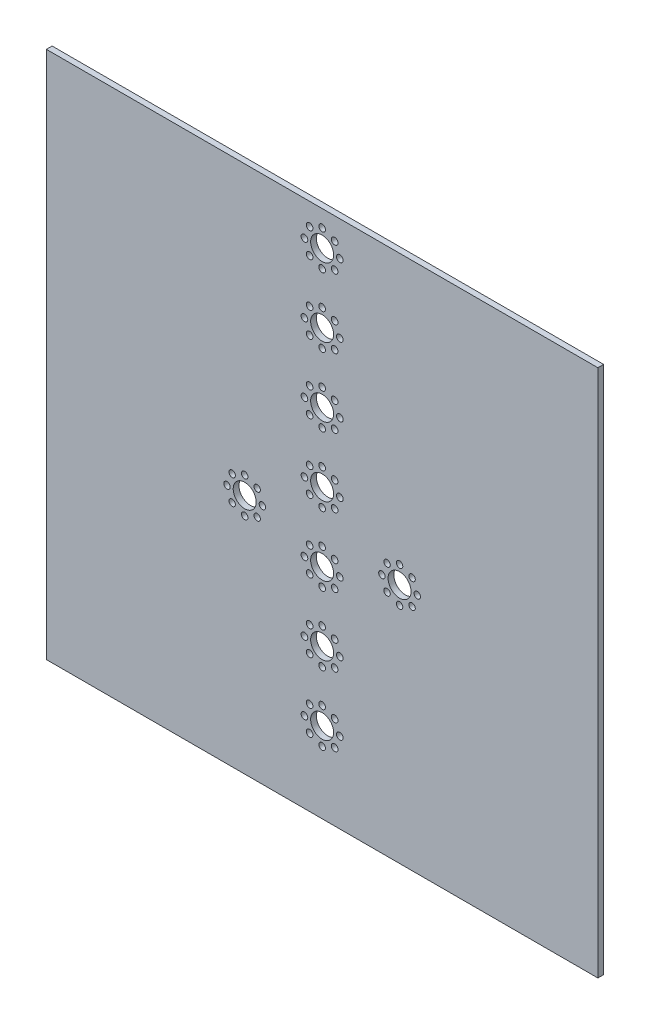
SolidWorks part; units mm, degrees
material "6061-T6 (SS)"
ref_plane "Front Plane" through (0, 0, 0) normal (0, 0, 1) x (1, 0, 0)
ref_plane "Top Plane" through (0, 0, 0) normal (0, 1, 0) x (1, 0, 0)
ref_plane "Right Plane" through (0, 0, 0) normal (1, 0, 0) x (0, 0, -1)
sketch "Sketch1" plane through (0, 0, 0) normal (0, 0, 1) x (1, 0, 0)
  line L1 (0, 0) -> (-304.8, 0)
  line L2 (0, 0) -> (0, -292.1)
  line L3 (0, -292.1) -> (-304.8, -292.1)
  line L4 (-304.8, 0) -> (-304.8, -292.1)
  dimension "D1" = 292.1
  dimension "D2" = 304.8
extrude "Boss-Extrude1" add sketch "Sketch1" along normal blind 3.175
sketch "Sketch2" plane through (0, 0, 0) normal (0, 0, -1) x (-1, 0, 0)
  line L0 (0, -158.75) -> (304.8, -158.75) construction
  line L1 (0, -292.1) -> (0, 0) construction
  line L2 (304.8, 0) -> (304.8, -292.1) construction
  line L3 (304.8, -292.1) -> (0, -292.1) construction
  circle A0 centre (99.822, -158.75) radius 1.778
  point P12 (109.601, -158.75)
  dimension "D2" = 109.601
  dimension "D3" = 3.556
  dimension "D1" = 133.35
  dimension "D5" = 9.779
extrude "Cut-Extrude1" cut sketch "Sketch2" against normal blind 3.175
ref_plane "Plane1" through (-152.4, 0, 0) normal (1, 0, 0) x (0, 0, -1)
mirror "Mirror1" about plane through (-152.4, 0, 0) normal (1, 0, 0) of "Cut-Extrude1"
sketch "Sketch3" plane through (0, 0, 0) normal (0, 0, -1) x (-1, 0, 0)
  line L2 (304.8, -292.1) -> (0, -292.1) construction
  line L3 (0, -292.1) -> (0, 0) construction
  circle A0 centre (109.601, -158.75) radius 6.35
  dimension "D3" = 12.7
  dimension "D1" = 133.35
  dimension "D2" = 109.601
extrude "Cut-Extrude2" cut sketch "Sketch3" against normal blind 3.175 contours A0
pattern_circular "CirPattern1" count 8 over 360 about axis through (-109.601, -158.75, 0) along (0, 0, -1) of "Cut-Extrude1"
mirror "Mirror2" about plane through (-152.4, 0, 0) normal (1, 0, 0) of "Cut-Extrude2", "CirPattern1"
sketch "Sketch4" plane through (0, 0, 0) normal (0, 0, -1) x (-1, 0, 0)
  line L0 (152.4, 1.7462) -> (152.4, -1.7463) construction
  line L1 (0, 0) -> (304.8, 0) construction
  circle A0 centre (152.4, -19.05) radius 6.35
  dimension "D1" = 12.7
  dimension "D2" = 19.05
extrude "Cut-Extrude3" cut sketch "Sketch4" against normal blind 3.175
sketch "Sketch5" plane through (0, 0, 0) normal (0, 0, -1) x (-1, 0, 0)
  line L0 (152.4, 1.7462) -> (152.4, -1.7463) construction
  circle A0 centre (152.4, -9.271) radius 1.8415
  circle A1 centre (152.4, -19.05) radius 6.35 construction
  dimension "D1" = 3.683
  dimension "D2" = 9.779
extrude "Cut-Extrude4" cut sketch "Sketch5" against normal blind 3.175
pattern_circular "CirPattern2" count 8 over 360 about axis through (-152.4, -19.05, 0) along (0, 0, -1) of "Cut-Extrude4"
pattern_linear "LPattern1" count 7 spacing 38.1 along (0, -1, 0) of "CirPattern2", "Cut-Extrude3"
